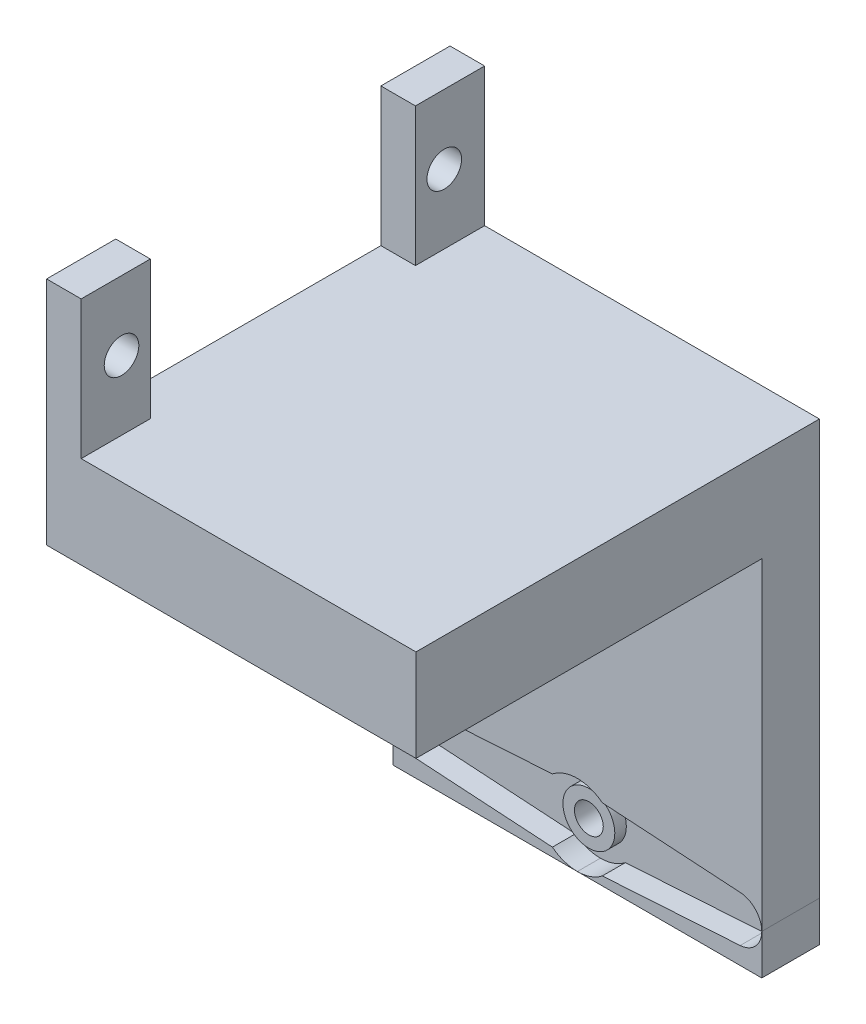
SolidWorks part; units mm, degrees
ref_plane "Front Plane" through (0, 0, 0) normal (0, 0, 1) x (1, 0, 0)
ref_plane "Top Plane" through (0, 0, 0) normal (0, 1, 0) x (1, 0, 0)
ref_plane "Right Plane" through (0, 0, 0) normal (1, 0, 0) x (0, 0, -1)
sketch "Sketch1" plane through (0, 0, 0) normal (0, 0, 1) x (1, 0, 0)
  line L0 (16, 0) -> (16, 36)
  line L1 (-2.1651, 2.75) -> (-14.1258, 1.996)
  line L2 (-14.1258, -1.996) -> (-2.1651, -2.75)
  line L3 (0, 4.7363) -> (0, -4.4899) construction
  line L4 (14.1258, -1.996) -> (2.1651, -2.75)
  line L5 (2.1651, 2.75) -> (14.1258, 1.996)
  line L6 (16, 36) -> (-16.0444, 36)
  line L7 (-16.0444, 36) -> (-16, 0)
  line L8 (-16, 0) -> (-16, -3.5)
  line L9 (-16, -3.5) -> (0, -3.5)
  line L10 (0, -3.5) -> (16, -3.5)
  line L11 (16, -3.5) -> (16, 0)
  line L12 (-16.0444, 36) -> (-16.0444, 48)
  line L13 (-16.0444, 48) -> (-13.0444, 48)
  line L14 (-13.0444, 48) -> (-13.0444, 36)
  line L15 (-16.0346, 28) -> (16, 28)
  circle A0 centre (0, 0) radius 2.25
  circle A1 centre (0, 0) radius 3.5
  arc A2 (-14.1258, 1.996) -> (-14.1258, -1.996) centre (-14, 0) ccw
  arc A3 (14.1258, 1.996) -> (14.1258, -1.996) centre (14, 0) cw
  circle A16 centre (0, 0) radius 1.25
  dimension "D1" = 7
  dimension "D2" = 4.5
  dimension "D4" = 28
  dimension "D5" = 2
  dimension "D10" = 2.5
  dimension "D11" = 28
  dimension "D3" = 5.5
  dimension "D12" = 32.0444
  dimension "D13" = 12
  dimension "D14" = 3
  dimension "D15" = 8
extrude "Boss-Extrude29" add sketch "Sketch1" along normal blind 30 and the other way blind 5 contours L7 L15 L0 L6 | L14 L13 L12 L6 region at (-0.0197, 32.0002, 0) region at (-14.5444, 42, 0)
extrude "Boss-Extrude31" add sketch "Sketch1<12>" against normal blind 5 contours L5 A3 L0 L15 L7 A2 L1 A1 | L11 A3 L4 A1 L10 | A2 L8 L9 A1 L2 region at (-0.0094, 15.1951, 0) region at (9.925, -2.8336, 0) region at (-9.925, -2.8336, 0)
sketch "Sketch1<12>" plane through (0, 0, 0) normal (0, 0, 1) x (1, 0, 0) same geometry as "Sketch1"
extrude "Boss-Extrude104" add sketch "Sketch1<23>" along normal mid plane 3 from offset 3.5 separate body contours A3 L5 A1 L4 | L1 A2 L2 A1 | L3 A1 A0 | A1 L3 A0 region at (8.9985, 0, 0) region at (-1.12, -3.2332, 0) region at (0.0783, -2.875, 0) region at (-8.9985, 0, 0) offset against normal yes
sketch "Sketch1<23>" plane through (0, 0, 0) normal (0, 0, 1) x (1, 0, 0) same geometry as "Sketch1"
extrude "Boss-Extrude105" add sketch "Sketch1<24>" against normal blind 2 from offset 1 separate body contours L3 A0 A16 | A0 L3 A16 region at (-2.1997, 0, 0) region at (0.0503, -1.75, 0) offset against normal yes
sketch "Sketch1<24>" plane through (0, 0, 0) normal (0, 0, 1) x (1, 0, 0) same geometry as "Sketch1"
sketch "Sketch3" plane through (-16.0444, 0, 0) normal (-1, 0, 0) x (0, 0, 1)
  line L0 (24, 48) -> (24, 36)
  line L1 (-5, 48) -> (30, 48) construction
  line L2 (-5, 36) -> (30, 36) construction
  line L3 (24, 36) -> (1, 36)
  line L4 (1, 36) -> (1, 48)
  line L5 (1, 48) -> (24, 48)
  line L6 (30, 36) -> (30, 48) construction
  dimension "D1" = 23
  dimension "D2" = 6
extrude "Cut-Extrude1" cut sketch "Sketch3" against normal through all
sketch "Sketch4" plane through (-16.0444, 0, 0) normal (-1, 0, 0) x (0, 0, 1)
  line L0 (1, 48) -> (1, 36) construction
  line L1 (24, 36) -> (24, 48) construction
  line L2 (-5, 48) -> (1, 48) construction
  circle A0 centre (-1.5, 42) radius 1.5
  circle A1 centre (26.5, 42) radius 1.5
  dimension "D1" = 3
  dimension "D2" = 3
  dimension "D3" = 2.5
  dimension "D4" = 2.5
  dimension "D5" = 6
extrude "Cut-Extrude2" cut sketch "Sketch4" against normal through all
